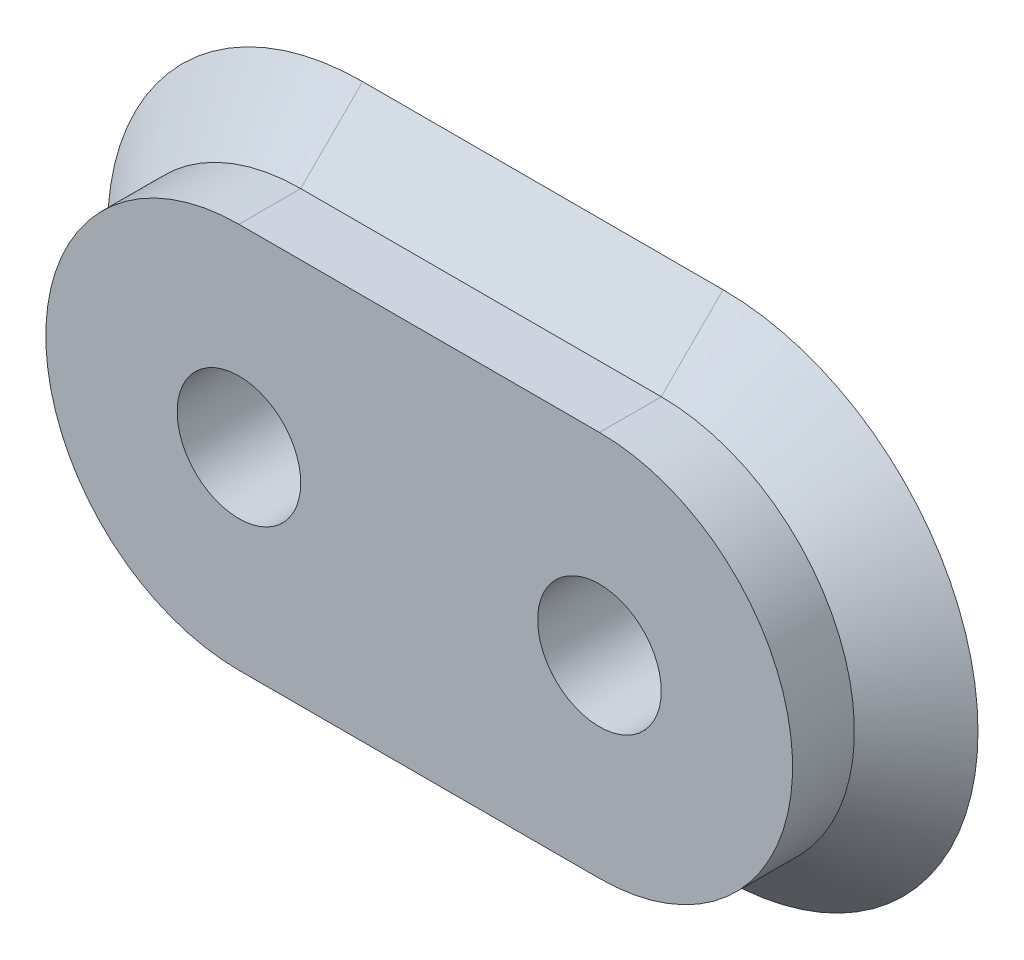
SolidWorks part; units mm, degrees
ref_plane "Front Plane" through (0, 0, 0) normal (0, 0, 1) x (1, 0, 0)
ref_plane "Top Plane" through (0, 0, 0) normal (0, 1, 0) x (1, 0, 0)
ref_plane "Right Plane" through (0, 0, 0) normal (1, 0, 0) x (0, 0, -1)
sketch "Sketch1" plane through (0, 0, 0) normal (0, 0, 1) x (1, 0, 0)
  line L0 (0, 0) -> (70, 0) construction
  line L1 (0, 37.5) -> (70, 37.5)
  line L2 (0, -37.5) -> (70, -37.5)
  arc A0 (0, 37.5) -> (0, -37.5) centre (0, 0) ccw
  arc A1 (70, -37.5) -> (70, 37.5) centre (70, 0) ccw
  point P3 (35, 0)
  dimension "D1" = 37.5
  dimension "D2" = 70
extrude "Boss-Extrude1" add sketch "Sketch1" along normal blind 12
sketch "Sketch2" plane through (0, 0, 0) normal (0, 0, -1) x (-1, 0, 0)
  line L0 (0, 0) -> (-70, 0) construction
  line L1 (0, -49.5) -> (-70, -49.5)
  line L2 (0, 49.5) -> (-70, 49.5)
  arc A0 (0, -49.5) -> (0, 49.5) centre (0, 0) ccw
  arc A1 (-70, 49.5) -> (-70, -49.5) centre (-70, 0) ccw
  point P3 (-35, 0)
  dimension "D1" = 49.5
  dimension "D2" = 70
extrude "Boss-Extrude2" add sketch "Sketch2" along normal blind 12
chamfer "Chamfer1" distance 12 angle 45 4 edges at (35, 49.5, 0) (119.5, 0, 0) (35, -49.5, 0) (-49.5, 0, 0)
sketch "Sketch3" plane through (0, 0, 12) normal (0, 0, 1) x (1, 0, 0)
  circle A0 centre (0, 0) radius 12
  circle A1 centre (70, 0) radius 12
  dimension "D2" = 24
  dimension "D1" = 70
extrude "Cut-Extrude1" cut sketch "Sketch3" against normal through all
